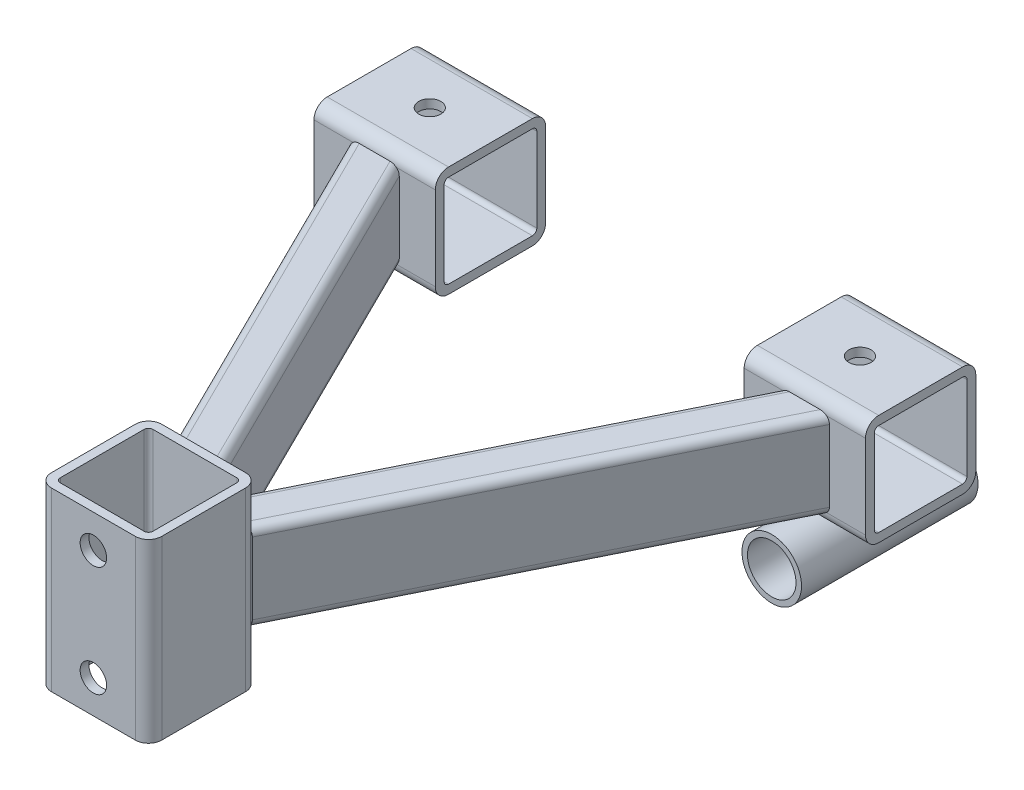
SolidWorks part; units mm, degrees
ref_plane "Спереди" through (0, 0, 0) normal (0, 0, 1) x (1, 0, 0)
ref_plane "Сверху" through (0, 0, 0) normal (0, 1, 0) x (1, 0, 0)
ref_plane "Справа" through (0, 0, 0) normal (1, 0, 0) x (0, 0, -1)
sketch "Эскиз1" plane through (0, 0, 0) normal (0, 1, 0) x (1, 0, 0)
  line L0 (70, 0) -> (125, 0)
  line L1 (0, 0) -> (0, 71.1765) construction
  line L2 (-70, 0) -> (-125, 0)
  point P5 (97.5, 0)
  dimension "D1" = 55
  dimension "D2" = 97.5
other "Труба bxbxs гост8639-82 50 X 50 X 4(1)"
ref_plane "Плоскость1" through (-70, 0, 0) normal (-1, 0, 0) x (0, 0, 1)
sketch "Sketch1" plane through (-70, 0, 0) normal (-1, 0, 0) x (0, 0, 1)
  line L0 (-19, -21) -> (19, -21)
  line L1 (-21, -19) -> (-21, 19)
  line L2 (19, 21) -> (-19, 21)
  line L3 (21, 19) -> (21, -19)
  line L4 (-19, -25) -> (19, -25)
  line L5 (-25, -19) -> (-25, 19)
  line L6 (19, 25) -> (-19, 25)
  line L7 (25, 19) -> (25, -19)
  arc A0 (25, 19) -> (19, 25) centre (19, 19) ccw
  arc A1 (19, -25) -> (25, -19) centre (19, -19) ccw
  arc A2 (-25, -19) -> (-19, -25) centre (-19, -19) ccw
  arc A3 (-19, 25) -> (-25, 19) centre (-19, 19) ccw
  arc A4 (-19, 21) -> (-21, 19) centre (-19, 19) ccw
  arc A5 (21, 19) -> (19, 21) centre (19, 19) ccw
  arc A6 (19, -21) -> (21, -19) centre (19, -19) ccw
  arc A7 (-21, -19) -> (-19, -21) centre (-19, -19) ccw
  point P0 (-25, 0)
  point P1 (25, 0)
  point P2 (0, 25)
  point P3 (0, -25)
  point P4 (0, 0)
  point P5 (-25, -25)
  point P6 (25, -25)
  point P7 (25, 25)
  point P8 (-25, 25)
  point P33 (0, 0)
  dimension "D1" = 6
  dimension "Thickness" = 4
  dimension "V_leg" = 50
sketch "Эскиз3" plane through (0, 0, 0) normal (0, 1, 0) x (1, 0, 0)
  line L0 (-97.5, -25) -> (0, -222.0905)
  line L1 (-125, -25) -> (-70, -25) construction
  line L2 (0, -222.0905) -> (97.5, -25)
  line L3 (70, -25) -> (125, -25) construction
  line L5 (97.5, -25) -> (-97.5, -25) construction
other "Труба axbxs гост8645-68 40 X 20 X 2.5(1)"
ref_plane "Плоскость2" through (-97.5, 0, 25) normal (0.4434, 0, 0.8963) x (0.8963, 0, -0.4434)
sketch "Sketch11" plane through (-97.5, 0, 25) normal (0.4434, 0, 0.8963) x (0.8963, 0, -0.4434)
  line L0 (-6.25, -17.5) -> (6.25, -17.5)
  line L1 (-7.5, -16.25) -> (-7.5, 16.25)
  line L2 (6.25, 17.5) -> (-6.25, 17.5)
  line L3 (7.5, 16.25) -> (7.5, -16.25)
  line L4 (-6.25, -20) -> (6.25, -20)
  line L5 (-10, -16.25) -> (-10, 16.25)
  line L6 (6.25, 20) -> (-6.25, 20)
  line L7 (10, 16.25) -> (10, -16.25)
  arc A0 (10, 16.25) -> (6.25, 20) centre (6.25, 16.25) ccw
  arc A1 (6.25, -20) -> (10, -16.25) centre (6.25, -16.25) ccw
  arc A2 (-10, -16.25) -> (-6.25, -20) centre (-6.25, -16.25) ccw
  arc A3 (-6.25, 20) -> (-10, 16.25) centre (-6.25, 16.25) ccw
  arc A4 (-6.25, 17.5) -> (-7.5, 16.25) centre (-6.25, 16.25) ccw
  arc A5 (7.5, 16.25) -> (6.25, 17.5) centre (6.25, 16.25) ccw
  arc A6 (6.25, -17.5) -> (7.5, -16.25) centre (6.25, -16.25) ccw
  arc A7 (-7.5, -16.25) -> (-6.25, -17.5) centre (-6.25, -16.25) ccw
  point P0 (0, 20)
  point P1 (10, 0)
  point P2 (0, -20)
  point P3 (-10, 0)
  point P4 (-10, 20)
  point P5 (10, 20)
  point P6 (10, -20)
  point P7 (-10, -20)
  point P8 (0, 0)
  point P33 (0, 0)
  dimension "D1" = 3.75
  dimension "Thickness" = 2.5
  dimension "V_leg" = 40
  dimension "H_leg" = 20
sketch "Эскиз6" plane through (0, 0, 0) normal (0, 1, 0) x (1, 0, 0)
  line L0 (0, -199.5379) -> (0, -25)
  line L1 (97.5, -25) -> (-97.5, -25) construction
other "Отсечь/Удлинить2"
other "Отсечь/Удлинить3"
ref_plane "Плоскость3" through (0, 0, 225) normal (0, 0, 1) x (1, 0, 0)
sketch "Эскиз7" plane through (0, 0, 225) normal (0, 0, 1) x (1, 0, 0)
  line L0 (0, -40) -> (0, 40)
  point P4 (0, 0)
  dimension "D1" = 80
other "Труба bxbxs гост8639-82 50 X 50 X 4(2)"
ref_plane "Плоскость4" through (0, -40, 225) normal (0, 1, 0) x (-1, 0, 0)
sketch "Sketch12" plane through (0, -40, 225) normal (0, 1, 0) x (-1, 0, 0)
  line L0 (-19, -21) -> (19, -21)
  line L1 (-21, -19) -> (-21, 19)
  line L2 (19, 21) -> (-19, 21)
  line L3 (21, 19) -> (21, -19)
  line L4 (-19, -25) -> (19, -25)
  line L5 (-25, -19) -> (-25, 19)
  line L6 (19, 25) -> (-19, 25)
  line L7 (25, 19) -> (25, -19)
  arc A0 (25, 19) -> (19, 25) centre (19, 19) ccw
  arc A1 (19, -25) -> (25, -19) centre (19, -19) ccw
  arc A2 (-25, -19) -> (-19, -25) centre (-19, -19) ccw
  arc A3 (-19, 25) -> (-25, 19) centre (-19, 19) ccw
  arc A4 (-19, 21) -> (-21, 19) centre (-19, 19) ccw
  arc A5 (21, 19) -> (19, 21) centre (19, 19) ccw
  arc A6 (19, -21) -> (21, -19) centre (19, -19) ccw
  arc A7 (-21, -19) -> (-19, -21) centre (-19, -19) ccw
  point P0 (-25, 0)
  point P1 (25, 0)
  point P2 (0, 25)
  point P3 (0, -25)
  point P4 (0, 0)
  point P5 (-25, -25)
  point P6 (25, -25)
  point P7 (25, 25)
  point P8 (-25, 25)
  point P33 (0, 0)
  dimension "D1" = 6
  dimension "Thickness" = 4
  dimension "V_leg" = 50
other "Отсечь/Удлинить4"
sketch "Эскиз9" plane through (0, 0, 250) normal (0, 0, 1) x (1, 0, 0)
  line L1 (0, -40) -> (0, -31) construction
  line L3 (0, 31) -> (0, 40) construction
  circle A0 centre (0, 25) radius 6
  circle A1 centre (0, -25) radius 6
  dimension "D1" = 12
  dimension "D2" = 50
extrude "Вырез-Вытянуть1" cut sketch "Эскиз9" against normal up to next (4 mm away) contours A1
sketch "Эскиз10" plane through (0, 0, 0) normal (0, 0, 1) x (1, 0, 0)
  line L1 (97.5, -25) -> (97.5, -68.2221) construction
  line L2 (70, -25) -> (125, -25) construction
  circle A0 centre (97.5, -38.5) radius 13.5
  circle A1 centre (97.5, -38.5) radius 11
  dimension "D1" = 22
  dimension "D2" = 27
extrude "Бобышка-Вытянуть1" add sketch "Эскиз10" along normal blind 40 and the other way blind 40 separate body
ref_plane "Плоскость5" through (0, -52, 0) normal (0, -1, 0) x (-1, 0, 0)
sketch "Эскиз11" plane through (0, -52, 0) normal (0, -1, 0) x (-1, 0, 0)
  line L0 (-84, 0) -> (-156.6087, 0) construction
  line L1 (-84, -40) -> (-84, 40) construction
  line L2 (-97.5, 40) -> (-97.5, -68.1007) construction
  line L3 (-84, 40) -> (-111, 40) construction
  circle A0 centre (-97.5, 0) radius 5
  dimension "D1" = 10
extrude "Вырез-Вытянуть2" cut sketch "Эскиз11" against normal up to next
sketch "Эскиз12" plane through (0, 25, 0) normal (0, 1, 0) x (1, 0, 0)
  line L0 (0, 0) -> (0, 14.7558) construction
  circle A0 centre (-97.5, 0) radius 5
  circle A1 centre (97.5, 0) radius 5
  dimension "D1" = 10
extrude "Вырез-Вытянуть3" cut sketch "Эскиз12" against normal up to next (4 mm away)
